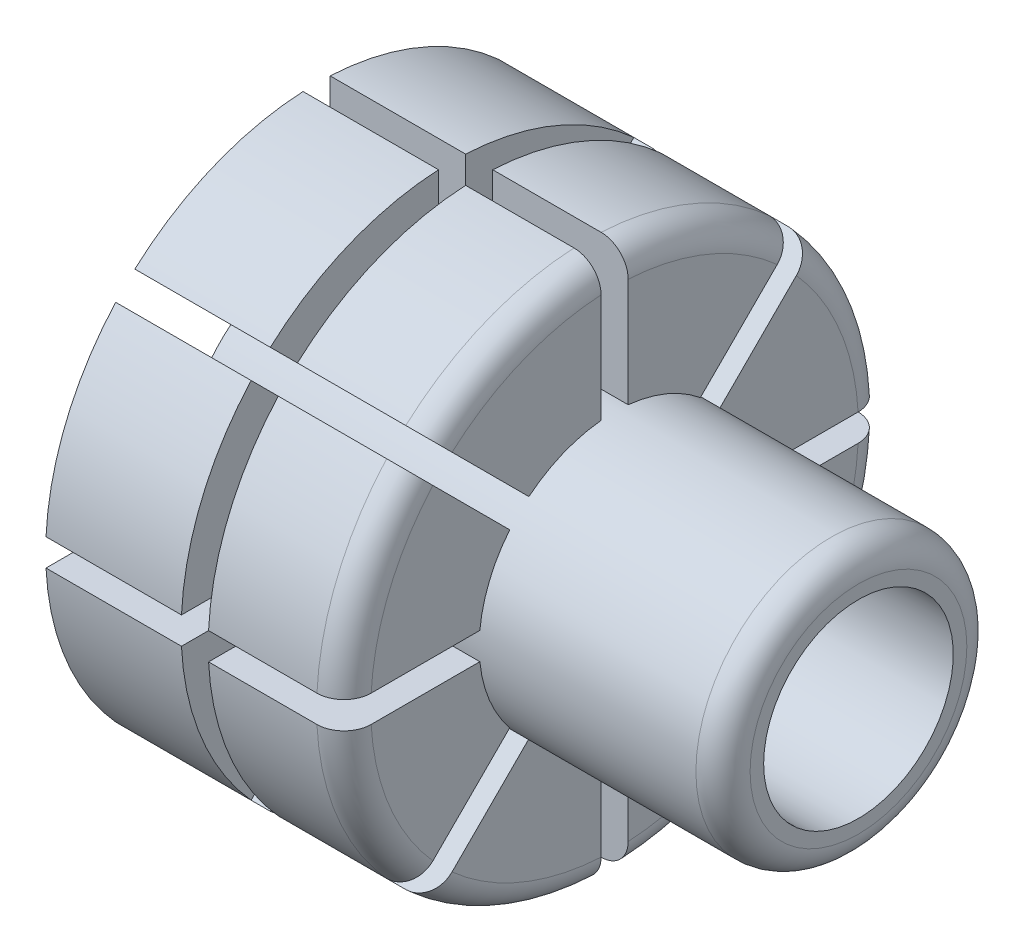
SolidWorks part; units mm, degrees
ref_plane "Piano frontale" through (0, 0, 0) normal (0, 0, 1) x (1, 0, 0)
ref_plane "Piano superiore" through (0, 0, 0) normal (0, 1, 0) x (1, 0, 0)
ref_plane "Piano destro" through (0, 0, 0) normal (1, 0, 0) x (0, 0, -1)
sketch "Schizzo1" plane through (0, 0, 0) normal (0, 0, 1) x (1, 0, 0)
  line L0 (-39.3095, 0) -> (43.9819, 0) construction
  line L1 (-18.601, 10) -> (-23.601, 10)
  line L2 (-3.601, 3.5) -> (-3.601, 4)
  line L3 (-4.601, 5) -> (-12.601, 5)
  line L4 (-12.601, 5) -> (-12.601, 9)
  line L5 (-13.601, 10) -> (-17.601, 10)
  line L6 (-23.601, 10) -> (-23.601, 3.5)
  line L7 (0, -55) -> (0, 55) construction
  line L8 (-18.601, 10) -> (-18.601, 6)
  line L9 (-18.601, 6) -> (-17.601, 6)
  line L10 (-17.601, 10) -> (-17.601, 6)
  line L11 (-23.601, 3.5) -> (-3.601, 3.5)
  arc A0 (-3.601, 4) -> (-4.601, 5) centre (-4.601, 4) ccw
  arc A1 (-12.601, 9) -> (-13.601, 10) centre (-13.601, 9) ccw
  dimension "D9" = 1
  dimension "D10" = 3.601
  dimension "D1" = 20
  dimension "D2" = 10
  dimension "D3" = 1
  dimension "D4" = 12
  dimension "D5" = 5
  dimension "D6" = 5
  dimension "D7" = 20
  dimension "D8" = 7
revolve "Rivoluzione1" add sketch "Schizzo1" angle 360 about L0
sketch "Schizzo2" plane through (-23.601, 0, 0) normal (-1, 0, 0) x (0, 0, 1)
  line L0 (0, 0) -> (0, 10.7527) construction
  line L1 (0.5, 4.9749) -> (0.5, 10.7527)
  line L2 (-0.5, 4.9749) -> (-0.5, 10.7527)
  line L3 (0.5, 0) -> (0.5, 10.7527) construction
  line L4 (-0.5, 0) -> (-0.5, 10.7527) construction
  line L5 (-0.5, 10.7527) -> (0.5, 10.7527)
  arc A1 (0.5, 4.9749) -> (-0.5, 4.9749) centre (0, 0) ccw
  circle A9 centre (0, 0) radius 5 construction
  point P40 (0, 0)
  dimension "D3" = 5.7778
  dimension "D1" = 0.5
  dimension "D2" = 0.5
extrude "Taglio-Estrusione1" cut sketch "Schizzo2" against normal through all
pattern_circular "RipetizioneCircolare1" count 8 over 360 about axis through (-39.3095, 0, 0) along (-1, 0, 0) of "Taglio-Estrusione1"
ref_axis "Assi1" through (-3.601, 0, 0) along (-1, 0, 0)
